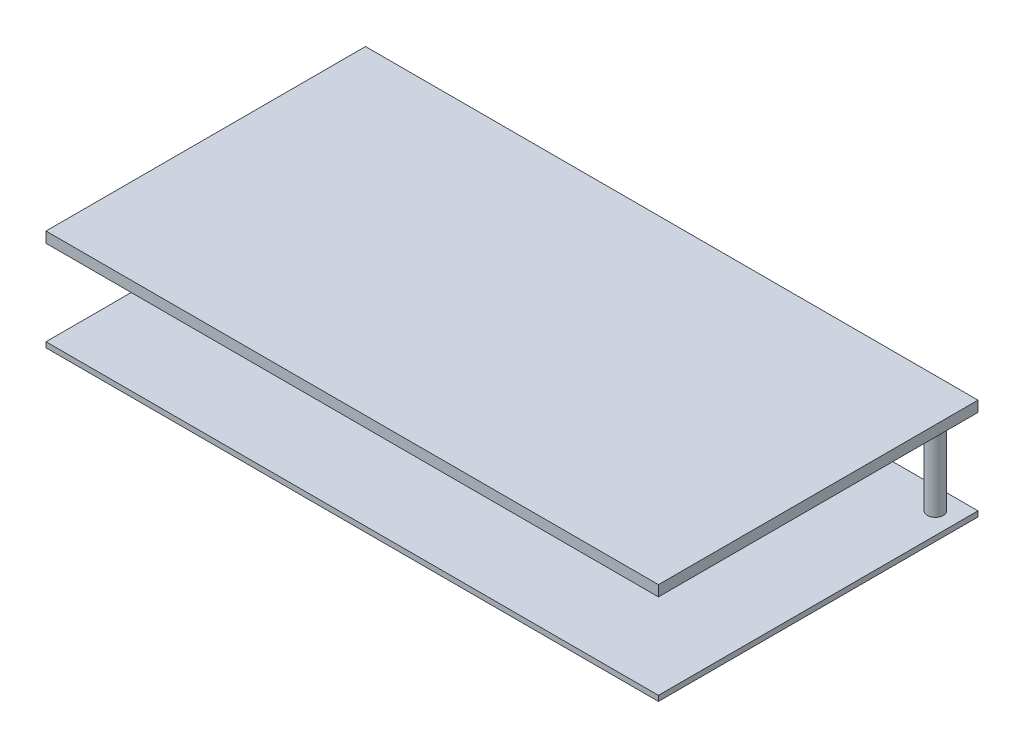
SolidWorks part; units mm, degrees
ref_plane "Piano frontale" through (0, 0, 0) normal (0, 0, 1) x (1, 0, 0)
ref_plane "Piano superiore" through (0, 0, 0) normal (0, 1, 0) x (1, 0, 0)
ref_plane "Piano destro" through (0, 0, 0) normal (1, 0, 0) x (0, 0, -1)
sketch "Schizzo1" plane through (0, 2, 0) normal (0, 1, 0) x (1, 0, 0)
  line L0 (-67.2848, 37.7082) -> (-193.7625, 37.7082) construction
  line L1 (-107.0625, 7.7082) -> (-222.0625, 7.7082)
  line L2 (-107.0625, 7.7082) -> (-107.0625, 67.7082)
  line L3 (-107.0625, 67.7082) -> (-222.0625, 67.7082)
  line L4 (-222.0625, 7.7082) -> (-222.0625, 67.7082)
  line L5 (-132.0625, -23.7918) -> (-132.0625, 108.3368) construction
  dimension "D1" = 60
  dimension "D2" = 30
  dimension "D3" = 25
  dimension "D4" = 115
extrude "Estrusione-Estrusione1" add sketch "Schizzo1" along normal blind 2 from offset 17 contours L2 L3 L4 L1
sketch "Schizzo5" plane through (0, 21, 0) normal (0, 1, 0) x (1, 0, 0)
  line L0 (-107.0625, 7.7082) -> (-107.0625, 67.7082) construction
  line L1 (-107.0625, 67.7082) -> (-222.0625, 67.7082) construction
  circle A0 centre (-111.0625, 63.7082) radius 1.5
  dimension "D1" = 4
  dimension "D2" = 4
extrude "Estrusione-Estrusione2" add sketch "Schizzo5" against normal up to surface (19 mm away)
sketch "Schizzo6" plane through (0, 21, 0) normal (0, 1, 0) x (1, 0, 0)
  line L0 (-107.0625, 67.7082) -> (-222.0625, 67.7082) construction
  line L1 (-222.0625, 7.7082) -> (-222.0625, 67.7082) construction
  circle A0 centre (-192.0625, 63.7082) radius 1.5
  dimension "D1" = 4
  dimension "D2" = 30
extrude "Estrusione-Estrusione3" add sketch "Schizzo6" against normal up to surface (19 mm away)
extrude "Estrusione-Estrusione4" add sketch "Schizzo1<3>" along normal blind 1
sketch "Schizzo1<3>" plane through (0, 2, 0) normal (0, 1, 0) x (1, 0, 0) same geometry as "Schizzo1"
ref_plane "Piano2" through (0, 11, 0) normal (0, -1, 0) x (-1, 0, 0)
